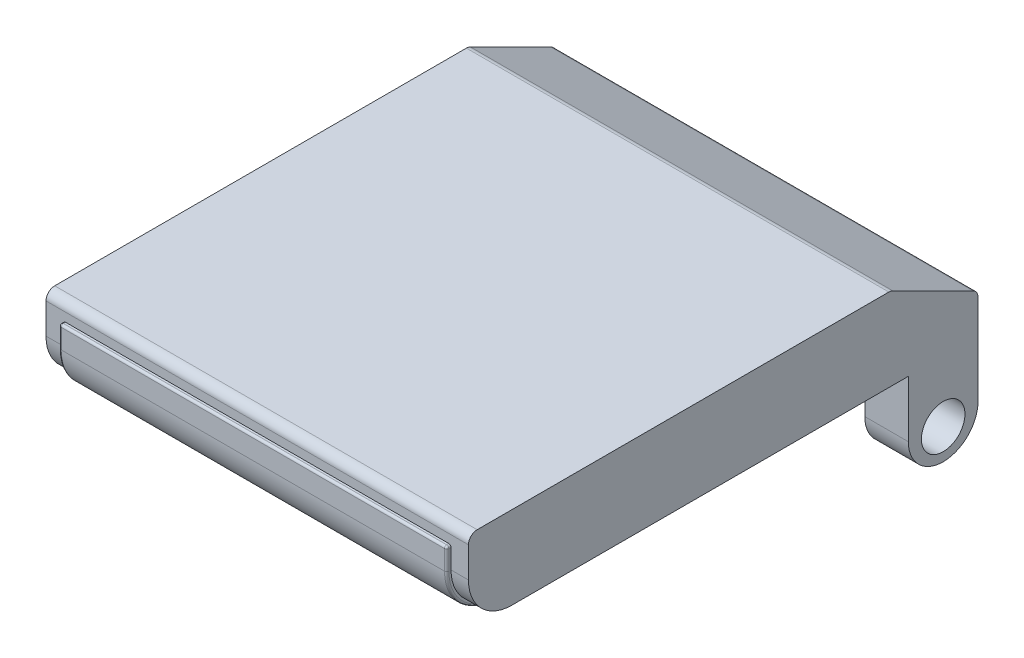
SolidWorks part; units mm, degrees
ref_plane "Front Plane" through (0, 0, 0) normal (0, 0, 1) x (1, 0, 0)
ref_plane "Top Plane" through (0, 0, 0) normal (0, 1, 0) x (1, 0, 0)
ref_plane "Right Plane" through (0, 0, 0) normal (1, 0, 0) x (0, 0, -1)
sketch "Sketch1" plane through (0, 0, 0) normal (0, 1, 0) x (1, 0, 0)
  line L0 (-406.1889, 0) -> (19903.2573, 0) construction
  line L1 (0, -406.1889) -> (0, 19903.2573) construction
  line L3 (-24.25, 29.25) -> (24.25, 29.25)
  line L4 (-24.25, 29.25) -> (-24.25, -29.25)
  line L5 (-24.25, -29.25) -> (24.25, -29.25)
  line L6 (24.25, 29.25) -> (24.25, -29.25)
  dimension "D1" = 58.5
  dimension "D2" = 48.5
extrude "Boss-Extrude1" add sketch "Sketch1" along normal blind 9.5
fillet "Fillet1" radius 5 1 edges at (0, 0, 29.25)
sketch "Sketch2" plane through (0, 0, 0) normal (1, 0, 0) x (0, 0, -1)
  line L3 (-29.75, 9.5) -> (-29.75, 5)
  line L4 (-29.75, 7.5) -> (-29.75, 5)
  line L5 (-29.75, 7.5) -> (-29.25, 7.5)
  line L6 (-24.25, -0.5) -> (29.25, -0.5)
  line L7 (-24.25, -0.5) -> (20.25, -0.5)
  line L8 (-29.25, 9.5) -> (-29.25, 5) construction
  line L9 (-29.25, 9.5) -> (29.25, 9.5) construction
  line L10 (20.25, 0) -> (20.25, -0.5)
  line L11 (-24.25, 0) -> (29.25, 0) construction
  line L12 (-24.25, 0) -> (20.25, 0)
  line L13 (-29.25, 7.5) -> (-29.25, 5)
  arc A1 (-29.25, 5) -> (-24.25, 0) centre (-24.25, 5) ccw construction
  arc A2 (-29.75, 5) -> (-24.25, -0.5) centre (-24.25, 5) ccw
  arc A3 (-29.75, 5) -> (-24.25, -0.5) centre (-24.25, 5) ccw
  arc A4 (-29.25, 5) -> (-24.25, 0) centre (-24.25, 5) ccw
  dimension "D3" = 2
  dimension "D4" = 50
  dimension "D1" = 0.5
  dimension "D2" = 0.5
extrude "Boss-Extrude2" add sketch "Sketch2" along normal offset from surface 2 and the other way offset from surface 2 up to face at (24.25, 4.5929, 5.0571) other way up to face at (-24.25, 4.5929, 5.0571)
fillet "Fillet2" radius 1 1 edges at (0, 9.5, 29.25)
fillet "Fillet3" radius 0.25 10 edges at (-22.25, -0.5, 2) (-22.25, 1.1109, 28.1391) (22.25, -0.5, 2) (22.25, 1.1109, 28.1391) (0, -0.5, -20.25) (-22.25, 6.25, 29.75) (-22.25, 7.5, 29.5) (22.25, 7.5, 29.5) (22.25, 6.25, 29.75) (0, 7.5, 29.75)
sketch "Sketch3" plane through (24.25, 0, 0) normal (1, 0, 0) x (0, 0, -1)
  line L0 (19.25, 9.5) -> (29.25, 4.5)
  line L1 (-28.25, 9.5) -> (29.25, 9.5) construction
  line L2 (29.25, 9.5) -> (29.25, 0) construction
  line L3 (29.25, 4.5) -> (29.25, 9.5)
  line L4 (29.25, 9.5) -> (19.25, 9.5)
  dimension "D1" = 10
  dimension "D2" = 5
extrude "Cut-Extrude1" cut sketch "Sketch3" against normal through all
fillet "Fillet4" radius 1 2 edges at (0, 4.5, -29.25) (0, 9.5, -19.25)
sketch "Sketch4" plane through (0, 0, 0) normal (1, 0, 0) x (0, 0, -1)
  line L0 (-22.25, -0.5) -> (-19.75, -3.5)
  line L1 (20, -0.5) -> (-24.25, -0.5) construction
  line L2 (-19.75, -3.5) -> (-17.25, -0.5)
  line L3 (-22.25, -0.5) -> (-17.25, -0.5)
  line L4 (-29.75, 5) -> (-29.75, 7.25) construction
  dimension "D1" = 5
  dimension "D2" = 3
  dimension "D3" = 10
extrude "Boss-Extrude3" add sketch "Sketch4" along normal offset from surface 4 and the other way offset from surface 4 up to face at (24.25, 5.5365, -1.507) other way up to face at (-24.25, 5.5365, -1.507)
ref_plane "Plane1" through (0, 0, 19.75) normal (0, 0, 1) x (-1, 0, 0)
sketch "Sketch5" plane through (0, 0, 19.75) normal (0, 0, 1) x (-1, 0, 0)
  line L0 (-20.25, 3.5) -> (-18.25, 3.5)
  line L1 (-20.25, 3.5) -> (20.25, 3.5) construction
  line L2 (-18.25, 3.5) -> (-20.25, 0.5)
  line L3 (-20.25, 0.5) -> (-20.25, 3.5)
  line L4 (0, -1000) -> (0, 49000) construction
  line L5 (20.25, 0.5) -> (20.25, 3.5)
  line L6 (18.25, 3.5) -> (20.25, 0.5)
  line L7 (20.25, 3.5) -> (18.25, 3.5)
  dimension "D1" = 2
extrude "Cut-Extrude2" cut sketch "Sketch5" against normal mid plane 5
ref_plane "Plane3" through (0, 0, -10.25) normal (0, 0, 1) x (-1, 0, 0)
sketch "Sketch8" plane through (0, 0, -10.25) normal (0, 0, 1) x (-1, 0, 0)
  line L0 (15.75, 0.5) -> (18.25, 0.5)
  line L1 (17.4818, 2.5781) -> (15.75, 0.5)
  line L2 (-20.25, 0.5) -> (20.25, 0.5) construction
  line L3 (18.25, 0.5) -> (18.25, 2.938)
  line L4 (18.25, -996.5) -> (18.25, 49003.5) construction
  line L5 (15.75, 0.5) -> (18.25, 3.5) construction
  arc A0 (18.25, 2.938) -> (17.4818, 2.5781) centre (18.25, 1.938) ccw
  dimension "D2" = 1
  dimension "D1" = 3
  dimension "D3" = 2.5
revolve "Revolve2" add sketch "Sketch8" angle 360 about L4
mirror "Mirror1" about plane through (0, 0, 0) normal (1, 0, 0) of "Revolve2"
fillet "Fillet8" radius 1 11 edges at (20.25, -0.5, 19.75) (-20.25, -0.5, 19.75) (-18.25, -0.5, -7.75) (19.25, -2, 21) (-19.25, -2, 21) (0, -0.5, 22.25) (19.25, -2, 18.5) (0, -0.5, 17.25) (-19.25, -2, 18.5) (0, -3.5, 19.75) (18.25, -0.5, -7.75)
sketch "Sketch10" plane through (24.25, 0, 0) normal (1, 0, 0) x (0, 0, -1)
  line L0 (-28.25, 9.5) -> (19.0139, 9.5) construction
  line L1 (29.25, 0) -> (21.25, 0)
  line L2 (29.25, 0) -> (29.25, -10.5)
  line L3 (29.25, -10.5) -> (21.25, -10.5)
  line L4 (21.25, 0) -> (21.25, -10.5)
  dimension "D1" = 20
  dimension "D2" = 8
extrude "Boss-Extrude4" add sketch "Sketch10" against normal blind 5
mirror "Mirror3" about plane through (0, 0, 0) normal (1, 0, 0) of "Boss-Extrude4"
sketch "Sketch12" plane through (0, 0, -29.25) normal (0, 0, -1) x (-1, 0, 0)
  line L0 (0, -1000) -> (0, 49000) construction
  line L3 (-6, -3) -> (-6, -10.5)
  line L4 (-6, -10.5) -> (6, -10.5)
  line L5 (6, -3) -> (6, -10.5)
  line L6 (-19.25, -10.5) -> (-24.25, -10.5) construction
  line L7 (19.25, -10.5) -> (19.25, 0) construction
  line L8 (-19.25, 0) -> (19.25, 0)
  line L9 (-19.25, 0) -> (-19.25, -3)
  line L10 (-19.25, -3) -> (-6, -3)
  line L14 (6, -3) -> (19.25, -3)
  line L15 (19.25, 0) -> (19.25, -3)
  dimension "D1" = 12
  dimension "D2" = 3
extrude "Boss-Extrude5" add sketch "Sketch12" against normal up to surface (8 mm away) up to face at (21.75, -5.25, -21.25)
sketch "Sketch13" plane through (24.25, 0, 0) normal (1, 0, 0) x (0, 0, -1)
  line L0 (25.25, -1010.5) -> (25.25, 48989.5) construction
  line L1 (21.25, -10.5) -> (29.25, -10.5) construction
  circle A0 centre (25.25, -7) radius 2.5
  point P5 (25.25, -10.5)
  dimension "D1" = 5
  dimension "D2" = 3.5
extrude "Cut-Extrude3" cut sketch "Sketch13" against normal through all
fillet "Fillet10" radius 4 6 edges at (-21.75, -10.5, -21.25) (-21.75, -10.5, -29.25) (0, -10.5, -29.25) (0, -10.5, -21.25) (21.75, -10.5, -21.25) (21.75, -10.5, -29.25)
fillet "Fillet11" radius 3 2 edges at (-12.625, -3, -21.25) (12.625, -3, -21.25)
fillet "Fillet12" radius 0.5 2 edges at (-12.625, -3, -29.25) (12.625, -3, -29.25)
sketch "Sketch16" plane through (0, -0.5, 0) normal (0, -1, 0) x (1, 0, 0)
  line L0 (22.25, 29.25) -> (24.25, 29.25) construction
  circle A0 centre (0, -5.75) radius 3.5
  dimension "D1" = 35
  dimension "D2" = 7
extrude "Cut-Extrude4" cut sketch "Sketch16" against normal blind 7
